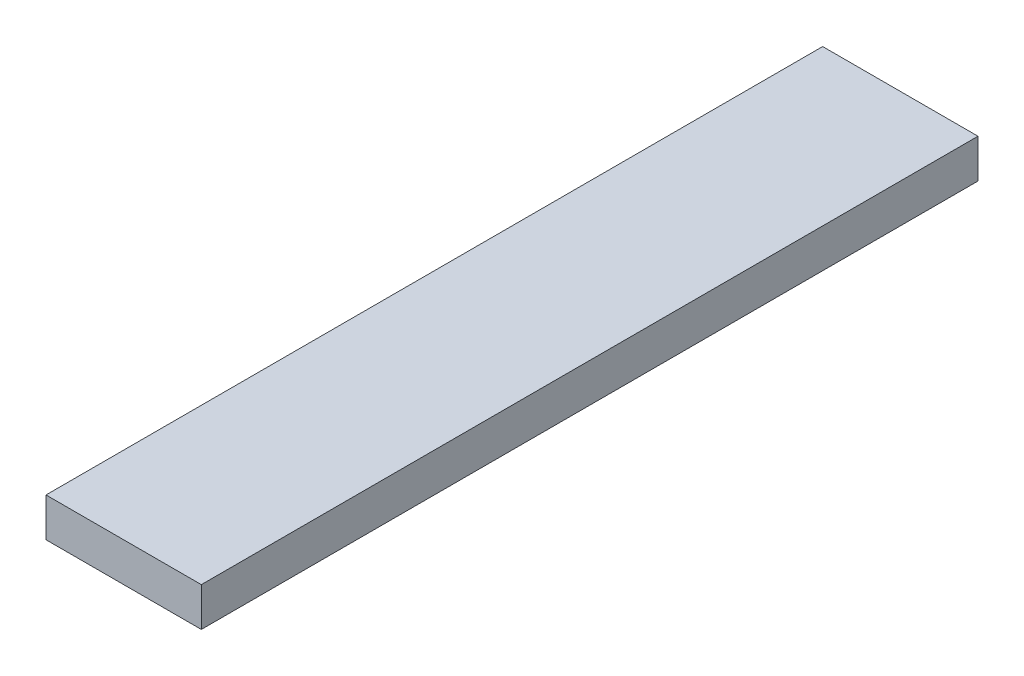
SolidWorks part; units mm, degrees
material "6061 Alloy"
ref_plane "Front Plane" through (0, 0, 0) normal (0, 0, 1) x (1, 0, 0)
ref_plane "Top Plane" through (0, 0, 0) normal (0, 1, 0) x (1, 0, 0)
ref_plane "Right Plane" through (0, 0, 0) normal (1, 0, 0) x (0, 0, -1)
sketch "Sketch1" plane through (0, 0, 0) normal (0, 1, 0) x (1, 0, 0)
  line L1 (-12.7, -63.5) -> (12.7, -63.5)
  line L2 (-12.7, -63.5) -> (-12.7, 63.5)
  line L3 (-12.7, 63.5) -> (12.7, 63.5)
  line L4 (12.7, -63.5) -> (12.7, 63.5)
  line L5 (-12.7, -63.5) -> (12.7, 63.5) construction
  line L6 (-12.7, 63.5) -> (12.7, -63.5) construction
  point P0 (0, 0)
  dimension "D1" = 127
  dimension "D2" = 25.4
extrude "Boss-Extrude1" add sketch "Sketch1" along normal blind 6.35
